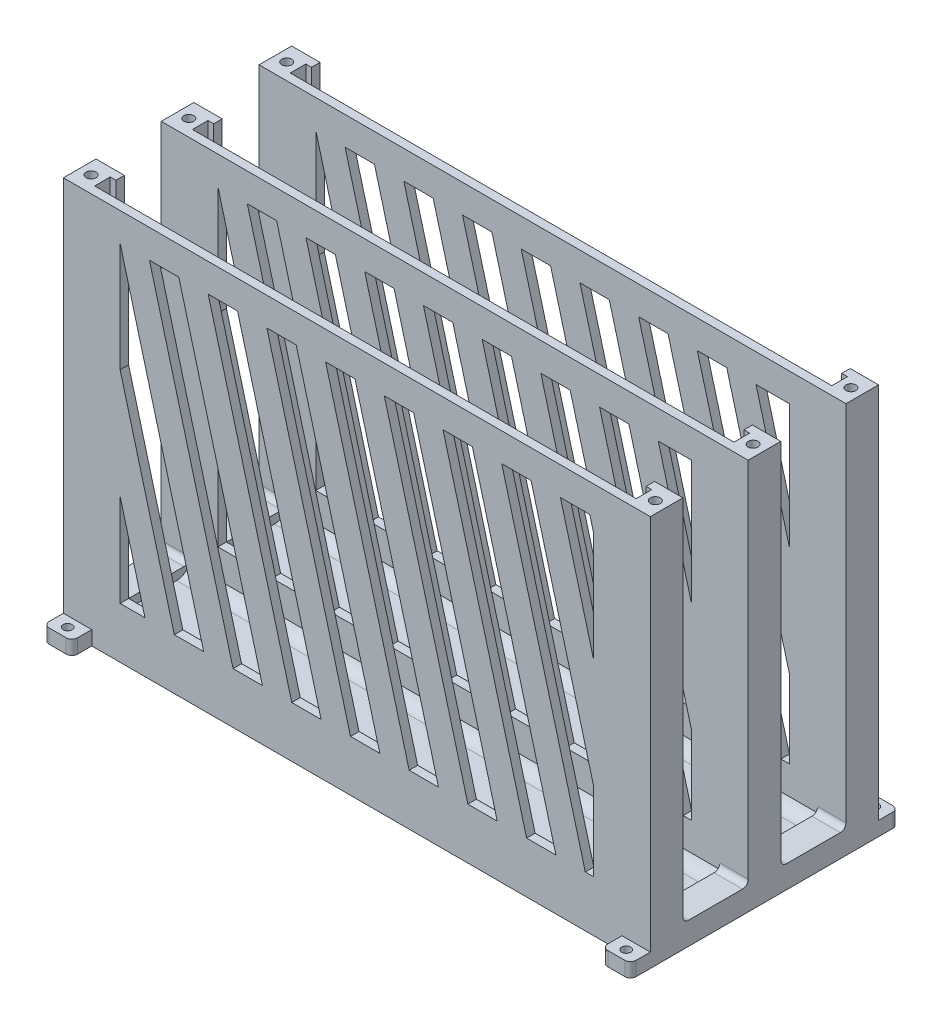
SolidWorks part; units mm, degrees
ref_plane "Front Plane" through (0, 0, 0) normal (0, 0, 1) x (1, 0, 0)
ref_plane "Top Plane" through (0, 0, 0) normal (0, 1, 0) x (1, 0, 0)
ref_plane "Right Plane" through (0, 0, 0) normal (1, 0, 0) x (0, 0, -1)
sketch "Sketch1" plane through (0, 0, 0) normal (0, 1, 0) x (1, 0, 0)
  line L0 (-95.5, 0) -> (95.5, 0) construction
  line L5 (-95.5, 2.75) -> (-93.5, 2.75)
  line L6 (-95.5, -2.75) -> (-95.5, 2.75)
  line L7 (-93.5, 2.75) -> (-93.5, 5.75)
  line L8 (-93.5, 5.75) -> (-103.5, 5.75)
  line L9 (-103.5, 5.75) -> (-103.5, -5.75)
  line L10 (-103.5, -5.75) -> (-93.5, -5.75)
  line L11 (-93.5, -5.75) -> (-93.5, -2.75)
  line L12 (-93.5, -2.75) -> (-95.5, -2.75)
  line L13 (-93.5, -2.75) -> (-93.5, -27.3056) construction
  line L14 (0, -55) -> (0, 55) construction
  line L15 (93.5, -5.75) -> (93.5, -2.75)
  line L16 (103.5, -5.75) -> (93.5, -5.75)
  line L17 (103.5, 5.75) -> (103.5, -5.75)
  line L18 (93.5, 5.75) -> (103.5, 5.75)
  line L19 (93.5, 2.75) -> (93.5, 5.75)
  line L20 (95.5, 2.75) -> (93.5, 2.75)
  line L21 (95.5, -2.75) -> (95.5, 2.75)
  line L22 (93.5, -2.75) -> (95.5, -2.75)
  line L23 (-93.5, 5.75) -> (93.5, 5.75)
  line L24 (-93.5, -5.75) -> (93.5, -5.75)
  line L25 (-93.5, -2.75) -> (93.5, -2.75)
  line L26 (93.5, 2.75) -> (-93.5, 2.75)
  line L27 (-93.5, -37.25) -> (-95.5, -37.25)
  line L28 (-95.5, -37.25) -> (-95.5, -31.75)
  line L29 (-95.5, -31.75) -> (-93.5, -31.75)
  line L30 (-93.5, -31.75) -> (-93.5, -28.75)
  line L31 (-93.5, -28.75) -> (-103.5, -28.75)
  line L32 (-103.5, -28.75) -> (-103.5, -40.25)
  line L33 (-103.5, -40.25) -> (-93.5, -40.25)
  line L34 (-93.5, -40.25) -> (-93.5, -37.25)
  line L35 (93.5, -40.25) -> (93.5, -37.25)
  line L36 (93.5, -37.25) -> (95.5, -37.25)
  line L37 (95.5, -37.25) -> (95.5, -31.75)
  line L38 (95.5, -31.75) -> (93.5, -31.75)
  line L39 (93.5, -31.75) -> (93.5, -28.75)
  line L40 (93.5, -28.75) -> (103.5, -28.75)
  line L41 (103.5, -28.75) -> (103.5, -40.25)
  line L42 (103.5, -40.25) -> (93.5, -40.25)
  line L43 (-93.5, -28.75) -> (93.5, -28.75)
  line L44 (93.5, -31.75) -> (-93.5, -31.75)
  line L45 (-93.5, -37.25) -> (93.5, -37.25)
  line L46 (-93.5, -40.25) -> (93.5, -40.25)
  line L47 (-93.5, -71.75) -> (-95.5, -71.75)
  line L48 (-95.5, -71.75) -> (-95.5, -66.25)
  line L49 (-95.5, -66.25) -> (-93.5, -66.25)
  line L50 (-93.5, -66.25) -> (-93.5, -63.25)
  line L51 (-93.5, -63.25) -> (-103.5, -63.25)
  line L52 (-103.5, -63.25) -> (-103.5, -74.75)
  line L53 (-103.5, -74.75) -> (-93.5, -74.75)
  line L54 (-93.5, -74.75) -> (-93.5, -71.75)
  line L55 (93.5, -74.75) -> (93.5, -71.75)
  line L56 (93.5, -71.75) -> (95.5, -71.75)
  line L57 (95.5, -71.75) -> (95.5, -66.25)
  line L58 (95.5, -66.25) -> (93.5, -66.25)
  line L59 (93.5, -66.25) -> (93.5, -63.25)
  line L60 (93.5, -63.25) -> (103.5, -63.25)
  line L61 (103.5, -63.25) -> (103.5, -74.75)
  line L62 (103.5, -74.75) -> (93.5, -74.75)
  line L63 (-93.5, -63.25) -> (93.5, -63.25)
  line L64 (93.5, -66.25) -> (-93.5, -66.25)
  line L65 (-93.5, -71.75) -> (93.5, -71.75)
  line L66 (-93.5, -74.75) -> (93.5, -74.75)
  line L67 (-103.5, -5.75) -> (-103.5, -28.75)
  line L68 (-93.5, -5.75) -> (-93.5, -28.75)
  line L69 (93.5, -5.75) -> (93.5, -28.75)
  line L70 (103.5, -5.75) -> (103.5, -28.75)
  line L71 (103.5, -40.25) -> (103.5, -63.25)
  line L72 (93.5, -63.25) -> (93.5, -40.25)
  line L73 (-103.5, -63.25) -> (-103.5, -40.25)
  line L74 (-93.5, -63.25) -> (-93.5, -40.25)
  line L75 (-103.5, 5.75) -> (-103.5, 10.75)
  line L76 (-101.5, 12.75) -> (-95.5, 12.75)
  line L77 (-93.5, 10.75) -> (-93.5, 5.75)
  line L78 (-98.5, 12.75) -> (-98.5, 5.75) construction
  line L79 (93.5, 10.75) -> (93.5, 5.75)
  line L80 (101.5, 12.75) -> (95.5, 12.75)
  line L81 (103.5, 5.75) -> (103.5, 10.75)
  line L82 (-103.5, -34.5) -> (103.5, -34.5) construction
  line L83 (-103.5, -74.75) -> (-103.5, -79.75)
  line L84 (-101.5, -81.75) -> (-95.5, -81.75)
  line L85 (-93.5, -79.75) -> (-93.5, -74.75)
  line L86 (-98.5, -74.75) -> (-98.5, -81.75) construction
  line L87 (101.5, -81.75) -> (95.5, -81.75)
  line L88 (93.5, -79.75) -> (93.5, -74.75)
  line L89 (103.5, -74.75) -> (103.5, -79.75)
  circle A0 centre (-98.5, 9.25) radius 1.6
  arc A1 (-95.5, 12.75) -> (-93.5, 10.75) centre (-95.5, 10.75) cw
  arc A2 (-103.5, 10.75) -> (-101.5, 12.75) centre (-101.5, 10.75) cw
  circle A3 centre (98.5, 9.25) radius 1.6
  arc A4 (95.5, 12.75) -> (93.5, 10.75) centre (95.5, 10.75) ccw
  arc A5 (103.5, 10.75) -> (101.5, 12.75) centre (101.5, 10.75) ccw
  circle A6 centre (-98.5, -78.25) radius 1.6
  arc A7 (-95.5, -81.75) -> (-93.5, -79.75) centre (-95.5, -79.75) ccw
  arc A8 (-101.5, -81.75) -> (-103.5, -79.75) centre (-101.5, -79.75) cw
  arc A9 (101.5, -81.75) -> (103.5, -79.75) centre (101.5, -79.75) ccw
  arc A10 (95.5, -81.75) -> (93.5, -79.75) centre (95.5, -79.75) cw
  circle A11 centre (98.5, -78.25) radius 1.6
  point P3 (0, 0)
  point P6 (95.5, 0)
  point P9 (-95.5, 0)
  point P66 (-103.5, 12.75)
  point P87 (-103.5, -81.75)
  dimension "D11" = 3.2
  dimension "D12" = 2
  dimension "D14" = 3.2
  dimension "D15" = 2
  dimension "D1" = 191
  dimension "D2" = 5.5
  dimension "D3" = 2
  dimension "D4" = 3
  dimension "D5" = 3
  dimension "D6" = 2
  dimension "D7" = 10
  dimension "D8" = 7
  dimension "D10" = 23
  dimension "D13" = 7
  dimension "D9" = 3
extrude "Boss-Extrude1" add sketch "Sketch1" against normal blind 3.2 contours L53 L54 L47 L48 L49 L50 L51 L52 | L54 L66 L55 L65 | L64 L59 L63 L50 | L34 L46 L35 L45 | L33 L34 L27 L28 L29 L30 L31 L32 | L44 L39 L43 L30 | L25 L11 L24 L15 | L26 L19 L23 L7 | L22 L15 L16 L17 L18 L19 L20 L21 | L42 L41 L40 L39 L38 L37 L36 L35 | L62 L61 L60 L59 L58 L57 L56 L55 | L11 L12 L6 L5 L7 L8 L9 L10 | L51 L74 L33 L73 | L68 L10 L67 L31 | L72 L60 L71 L42 | L70 L16 L69 L40 region at (-98.9231, 0, 0) region at (0, 0, -4.25) region at (98.9231, 0, 0) region at (0, 0, 4.25) region at (-98.5, 0, 17.25) region at (98.5, 0, 17.25) region at (0, 0, 30.25) region at (-98.9231, 0, 34.5) region at (98.9231, 0, 34.5) region at (-98.5, 0, 51.75) region at (0, 0, 38.75) region at (-98.9231, 0, 69) region at (98.5, 0, 51.75) region at (0, 0, 64.75) region at (98.9231, 0, 69) region at (0, 0, 73.25)
extrude "Boss-Extrude2" add sketch "Sketch1<4>" along normal blind 130 contours L53 L54 L47 L48 L49 L50 L51 L52 | L33 L34 L27 L28 L29 L30 L31 L32 | L11 L12 L6 L5 L7 L8 L9 L10 | L62 L61 L60 L59 L58 L57 L56 L55 | L42 L41 L40 L39 L38 L37 L36 L35 | L22 L15 L16 L17 L18 L19 L20 L21 region at (-98.9231, 0, 0) region at (98.9231, 0, 0) region at (-98.9231, 0, 34.5) region at (98.9231, 0, 34.5) region at (-98.9231, 0, 69) region at (98.9231, 0, 69)
sketch "Sketch1<4>" plane through (0, 0, 0) normal (0, 1, 0) x (1, 0, 0) same geometry as "Sketch1"
extrude "Boss-Extrude3" add sketch "Sketch1<5>" against normal blind 5 from offset 3 contours L53 L54 L47 L48 L49 L50 L51 L52 | L54 L66 L55 L65 | L47 L65 L56 L57 L58 L64 L49 L48 | L64 L59 L63 L50 | L51 L74 L33 L73 | L33 L34 L27 L28 L29 L30 L31 L32 | L34 L46 L35 L45 | L44 L39 L43 L30 | L68 L10 L67 L31 | L11 L12 L6 L5 L7 L8 L9 L10 | L25 L11 L24 L15 | L26 L19 L23 L7 | L22 L15 L16 L17 L18 L19 L20 L21 | L70 L16 L69 L40 | L42 L41 L40 L39 L38 L37 L36 L35 | L72 L60 L71 L42 | L62 L61 L60 L59 L58 L57 L56 L55 | L27 L45 L36 L37 L38 L44 L29 L28 | L20 L26 L5 L6 L12 L25 L22 L21 | L74 L63 L72 L46 | L69 L24 L68 L43 | A8 L84 A7 L85 L53 L83 A6 | A10 L87 A9 L89 L62 L88 A11 | L81 A5 L80 A4 L79 L18 A3 | A2 L75 L8 L77 A1 L76 A0 region at (-98.9231, 0, 0) region at (0, 0, 0) region at (0, 0, -4.25) region at (-98.5, 0, -5.8721) region at (98.9231, 0, 0) region at (0, 0, 4.25) region at (93.6221, 0, -8.25) region at (-98.5, 0, 17.25) region at (0, 0, 17.25) region at (98.5, 0, 17.25) region at (0, 0, 30.25) region at (-98.9231, 0, 34.5) region at (98.9231, 0, 34.5) region at (0, 0, 34.5) region at (-98.5, 0, 51.75) region at (0, 0, 38.75) region at (0, 0, 51.75) region at (-98.9231, 0, 69) region at (98.5, 0, 51.75) region at (0, 0, 64.75) region at (-98.5, 0, 74.8721) region at (98.9231, 0, 69) region at (0, 0, 69) region at (0, 0, 73.25) region at (103.3779, 0, 77.25) offset against normal yes
sketch "Sketch1<5>" plane through (0, 0, 0) normal (0, 1, 0) x (1, 0, 0) same geometry as "Sketch1"
fillet "Fillet1" radius 5 4 edges at (0, -3, 28.75) (0, -3, 5.75) (0, -3, 40.25) (0, -3, 63.25)
sketch "Sketch2" plane through (0, 130, 0) normal (0, 1, 0) x (1, 0, 0)
  line L0 (-95.5, 2.75) -> (-103.5, 2.75) construction
  line L1 (-103.5, 5.75) -> (-103.5, -5.75) construction
  line L2 (-95.5, -2.75) -> (-103.5, -2.75) construction
  line L3 (-99.5, 2.75) -> (-99.5, -2.75) construction
  line L4 (0, -55) -> (0, 55) construction
  line L5 (-95.5, -31.75) -> (-103.5, -31.75) construction
  line L6 (-103.5, -28.75) -> (-103.5, -40.25) construction
  line L7 (-95.5, -37.25) -> (-103.5, -37.25) construction
  line L8 (-99.5, -31.75) -> (-99.5, -37.25) construction
  circle A0 centre (-99.5, 0) radius 1.75
  circle A1 centre (99.5, 0) radius 1.75
  circle A2 centre (-99.5, -34.5) radius 1.75
  circle A3 centre (99.5, -34.5) radius 1.75
  circle A4 centre (-99.5, -69) radius 1.75
  circle A5 centre (99.5, -69) radius 1.75
  dimension "D1" = 3.5
  dimension "D3" = 34.5
  dimension "D2" = 3
extrude "Cut-Extrude1" cut sketch "Sketch2" against normal blind 5
fillet "Fillet2" radius 2 8 edges at (-98.5, 0, 5.75) (-98.5, 0, 40.25) (-98.5, 0, 28.75) (-98.5, 0, 63.25) (98.5, 0, 28.75) (98.5, 0, 5.75) (98.5, 0, 40.25) (98.5, 0, 63.25)
sketch "Sketch3" plane through (0, 0, 74.75) normal (0, 0, 1) x (1, 0, 0)
  line L0 (-93.5, 130) -> (93.5, 130)
  line L1 (-93.5, 130) -> (93.5, 0) construction
  line L2 (-93.5, 130) -> (93.5, 130)
  line L3 (-93.5, 130) -> (-93.5, 0)
  line L4 (-93.5, 0) -> (93.5, 0)
  line L5 (93.5, 130) -> (93.5, 0)
  line L6 (-83.5, 120) -> (-54.0256, 10)
  line L7 (-83.5, 10) -> (83.5, 10)
  line L8 (-83.5, 10) -> (-83.5, 120)
  line L9 (-83.5, 120) -> (83.5, 120)
  line L10 (83.5, 10) -> (83.5, 120)
  line L11 (0, 120) -> (0, 10) construction
  line L12 (-83.5, 65) -> (83.5, 65) construction
  line L13 (-73.1472, 120) -> (-43.6728, 10)
  line L14 (-52.4417, 120) -> (-22.9673, 10)
  line L15 (-62.7945, 120) -> (-33.3201, 10)
  line L16 (-31.7362, 120) -> (-2.2618, 10)
  line L17 (-42.089, 120) -> (-12.6145, 10)
  line L18 (-11.0307, 120) -> (18.4437, 10)
  line L19 (-21.3834, 120) -> (8.091, 10)
  line L20 (9.6749, 120) -> (39.1493, 10)
  line L21 (-0.6779, 120) -> (28.7965, 10)
  line L22 (30.3804, 120) -> (59.8548, 10)
  line L23 (20.0276, 120) -> (49.502, 10)
  line L24 (51.0859, 120) -> (80.5603, 10)
  line L25 (40.7331, 120) -> (70.2076, 10)
  line L26 (71.7914, 120) -> (83.5, 76.303)
  line L27 (61.4387, 120) -> (83.5, 37.666)
  line L29 (82.1442, 120) -> (83.5, 114.94)
  line L30 (-64.3784, 10) -> (-83.5, 81.363)
  line L31 (-83.5, 42.7259) -> (-74.7311, 10)
  line L32 (90.912, 125.9151) -> (92.0066, 121.8301) [skipped]
  point P6 (0, 65)
  point P40 (61.4474, 120)
  point P44 (67.887, 125)
  point P51 (78.2398, 125)
  point P52 (0, 0)
  line M38 (93.5, 130) -> (93.5, 0)
  line M39 (93.5, 0) -> (-93.5, 0)
  line M40 (-93.5, 0) -> (-93.5, 130)
  dimension "D1" = 10
  dimension "D2" = 10
  dimension "D3" = 15
  dimension "D4" = 10
  dimension "D6" = 10
  dimension "D7" = 10
  dimension "D8" = 10
  dimension "D5" = 9
extrude "Boss-Extrude4" add sketch "Sketch3" against normal up to vertex (3 mm away) contours L0 L10 L7 L8 L9 M40 M39 M38 | L8 L31 L7 L30 | L13 L9 L6 L7 | L9 L15 L7 L14 | L9 L17 L7 L16 | L9 L19 L7 L18 | L9 L21 L7 L20 | L9 L23 L7 L22 | L9 L25 L7 L24 | L9 L27 L10 L26 | L9 L29 L10 region at (0, 127.7225, 74.75) region at (-63.5864, 65, 74.75) region at (-76.2071, 37.2174, 74.75) region at (-42.8809, 65, 74.75) region at (-22.1754, 65, 74.75) region at (-1.4698, 65, 74.75) region at (19.2357, 65, 74.75) region at (39.9412, 65, 74.75) region at (60.6467, 65, 74.75) region at (74.793, 87.5052, 74.75) region at (83.0481, 118.3133, 74.75) up to point (-95.5, -3, 71.75)
sketch "Sketch4" plane through (0, 0, 40.25) normal (0, 0, 1) x (1, 0, 0)
  line L0 (-93.5, 130) -> (93.5, 0) construction
  line L1 (-93.5, 130) -> (93.5, 130)
  line L2 (-93.5, 130) -> (-93.5, 0)
  line L3 (-93.5, 0) -> (93.5, 0)
  line L4 (93.5, 130) -> (93.5, 0)
  line L5 (-83.5, 120) -> (-54.0256, 10)
  line L6 (-83.5, 10) -> (83.5, 10)
  line L7 (-83.5, 10) -> (-83.5, 120)
  line L8 (-83.5, 120) -> (83.5, 120)
  line L9 (83.5, 10) -> (83.5, 120)
  line L10 (0, 120) -> (0, 10) construction
  line L11 (-83.5, 65) -> (83.5, 65) construction
  line L12 (-73.1472, 120) -> (-43.6728, 10)
  line L13 (-52.4417, 120) -> (-22.9673, 10)
  line L14 (-62.7945, 120) -> (-33.3201, 10)
  line L15 (-31.7362, 120) -> (-2.2618, 10)
  line L16 (-42.089, 120) -> (-12.6145, 10)
  line L17 (-11.0307, 120) -> (18.4437, 10)
  line L18 (-21.3834, 120) -> (8.091, 10)
  line L19 (9.6749, 120) -> (39.1493, 10)
  line L20 (-0.6779, 120) -> (28.7965, 10)
  line L21 (30.3804, 120) -> (59.8548, 10)
  line L22 (20.0276, 120) -> (49.502, 10)
  line L23 (51.0859, 120) -> (80.5603, 10)
  line L24 (40.7331, 120) -> (70.2076, 10)
  line L25 (71.7914, 120) -> (83.5, 76.303)
  line L26 (61.4387, 120) -> (83.5, 37.666)
  line L27 (-64.3784, 10) -> (-83.5, 81.363)
  line L28 (-74.7311, 10) -> (-83.5, 42.7259)
  line L29 (92.497, 120) -> (93.5, 116.2566) [skipped]
  line L30 (82.1442, 120) -> (83.5, 114.94) [skipped]
  point P5 (0, 65)
  line M15 (93.5, 130) -> (93.5, 2)
  dimension "D1" = 10
  dimension "D2" = 10
  dimension "D3" = 15
  dimension "D4" = 10
  dimension "D6" = 10
  dimension "D7" = 10
  dimension "D8" = 10
  dimension "D5" = 9
extrude "Boss-Extrude5" add sketch "Sketch4" against normal blind 3 contours L4 L1 L2 L3 L9 L6 L7 L8 M15 | L12 L8 L5 L6 | L28 L6 L27 L7 | L8 L14 L6 L13 | L8 L16 L6 L15 | L8 L18 L6 L17 | L8 L20 L6 L19 | L8 L22 L6 L21 | L8 L24 L6 L23 | L8 L26 L9 L25 region at (0, 127.7225, 40.25) region at (-63.5864, 65, 40.25) region at (-76.2071, 37.2174, 40.25) region at (-42.8809, 65, 40.25) region at (-22.1754, 65, 40.25) region at (-1.4698, 65, 40.25) region at (19.2357, 65, 40.25) region at (39.9412, 65, 40.25) region at (60.6467, 65, 40.25) region at (74.793, 87.5052, 40.25)
pattern_linear "LPattern1" count 2 spacing 34.5 along (0, 0, -1) of "Boss-Extrude5"
